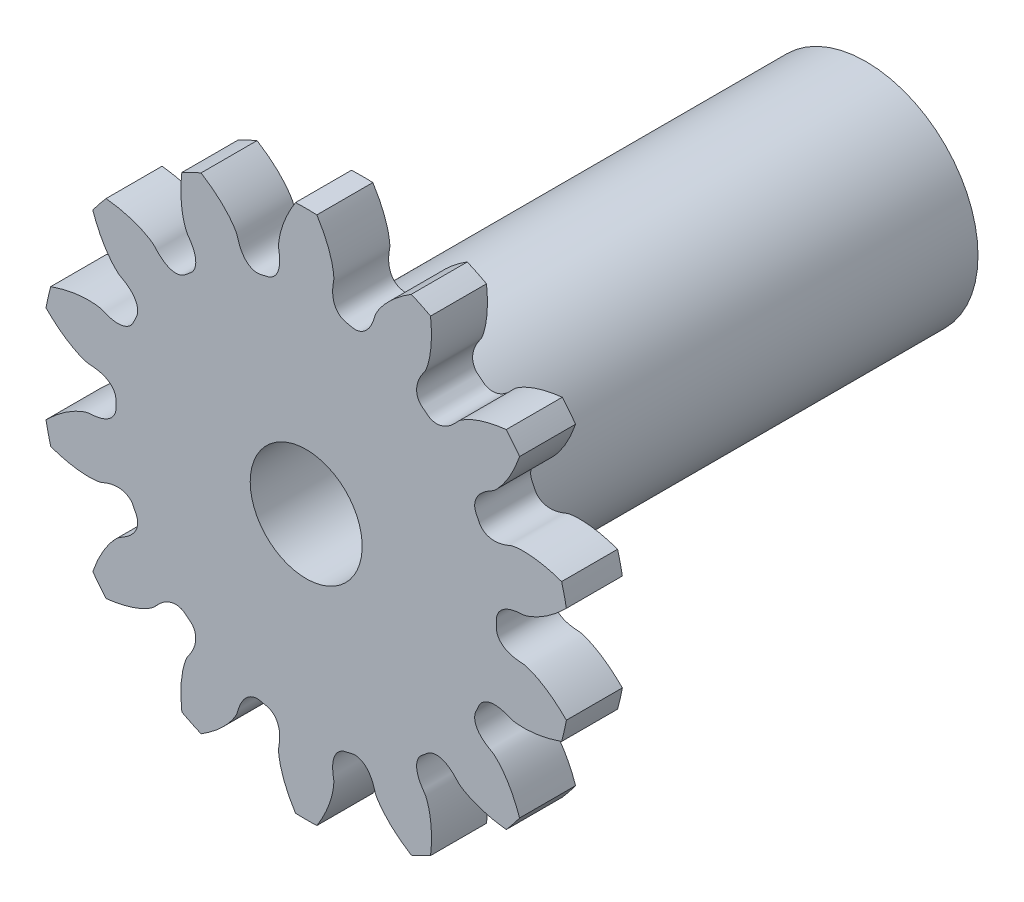
SolidWorks part; units mm, degrees
ref_plane "Alzado" through (0, 0, 0) normal (0, 0, 1) x (1, 0, 0)
ref_plane "Planta" through (0, 0, 0) normal (0, 1, 0) x (1, 0, 0)
ref_plane "Vista lateral" through (0, 0, 0) normal (1, 0, 0) x (0, 0, -1)
ref_axis "Eje1" through (0, 0, 55) along (0, 0, -1)
sketch "SketchRevolveSpur02" plane through (0, 0, 0) normal (1, 0, 0) x (0, 0, -1)
  line L0 (0, 0) -> (1, 0) construction
  line L1 (-0.5, 0) -> (-0.5, 1.1818)
  line L2 (-0.5, 1.1818) -> (-0.25, 1.1818)
  line L3 (-0.25, 1.1818) -> (-0.25, 0)
  line L4 (-0.25, 0) -> (-0.5, 0)
  dimension "D1" = 0.25
revolve "Spur02" add sketch "SketchRevolveSpur02" angle 360 about L0
sketch "SketchToothSpur02" plane through (0, 0, 0) normal (0, 0, 1) x (1, 0, 0)
  arc A0 (1.1682, 0.2227) -> (1.1682, -0.2227) centre (0, 0) cw
  spline S0 degree 3 poles (1.1682, -0.2227) (1.1575, -0.2117) (1.1414, -0.1961) (1.1195, -0.1771) (1.104, -0.1645) (1.089, -0.1533) (1.0747, -0.1432) (1.061, -0.1344) (1.048, -0.1266) (1.0358, -0.1199) (1.0245, -0.1142) (1.014, -0.1093) (1.0046, -0.1054) (0.9961, -0.1021) (0.9887, -0.0996) (0.9823, -0.0977) (0.9738, -0.0954) (0.9644, -0.0944) (0.9543, -0.0941) (0.9465, -0.0934) (0.9389, -0.0924) (0.9315, -0.0913) (0.9244, -0.0898) (0.9175, -0.0881) (0.9108, -0.0861) (0.9043, -0.0838) (0.8981, -0.0813) (0.892, -0.0784) (0.8862, -0.0751) (0.8806, -0.0714) (0.8752, -0.0673) (0.87, -0.0627) (0.8651, -0.0575) (0.8606, -0.0516) (0.8566, -0.0449) (0.8533, -0.0376) (0.8508, -0.0295) (0.8496, -0.0218) (0.8491, -0.0119) (0.8497, 0) (0.8491, 0.0119) (0.8496, 0.0218) (0.8508, 0.0295) (0.8533, 0.0376) (0.8566, 0.0449) (0.8606, 0.0516) (0.8651, 0.0575) (0.87, 0.0627) (0.8752, 0.0673) (0.8806, 0.0714) (0.8862, 0.0751) (0.892, 0.0784) (0.8981, 0.0813) (0.9043, 0.0838) (0.9108, 0.0861) (0.9175, 0.0881) (0.9244, 0.0898) (0.9315, 0.0913) (0.9389, 0.0924) (0.9465, 0.0934) (0.9543, 0.0941) (0.9644, 0.0944) (0.9738, 0.0954) (0.9823, 0.0977) (0.9887, 0.0996) (0.9961, 0.1021) (1.0046, 0.1054) (1.014, 0.1093) (1.0245, 0.1142) (1.0358, 0.1199) (1.048, 0.1266) (1.061, 0.1344) (1.0747, 0.1432) (1.089, 0.1533) (1.104, 0.1645) (1.1195, 0.1771) (1.1414, 0.1961) (1.1575, 0.2117) (1.1682, 0.2227) knots 0 0 0 0 0.0554 0.080914 0.104969 0.127567 0.148706 0.168388 0.186612 0.203378 0.218686 0.232536 0.244928 0.255863 0.265339 0.273357 0.279918 0.297272 0.307044 0.316542 0.325781 0.334777 0.343546 0.352112 0.360499 0.368737 0.376863 0.384917 0.39295 0.401018 0.409187 0.41753 0.426123 0.43504 0.444343 0.454063 0.464189 0.474651 0.482386 0.5 0.517614 0.525349 0.535811 0.545937 0.555657 0.56496 0.573877 0.58247 0.590813 0.598982 0.60705 0.615083 0.623137 0.631263 0.639501 0.647888 0.656454 0.665223 0.674219 0.683458 0.692956 0.702728 0.720082 0.726643 0.734661 0.744137 0.755072 0.767464 0.781314 0.796622 0.813388 0.831612 0.851294 0.872433 0.895031 0.919086 0.9446 1 1 1 1
extrude "ToothExtrudeCutSpur02" cut sketch "SketchToothSpur02" against normal blind 0.5 and the other way blind 0.5
pattern_circular "PatternSpur02" count 14 every 25.714 about axis through (0, 0, 55) along (0, 0, -1) of "ToothExtrudeCutSpur02"
sketch "AuxiliarySketchSpur02" plane through (0, 0, 0) normal (0, 0, 1) x (1, 0, 0)
  circle A0 centre (0, 0) radius 1.0341 construction
  circle A1 centre (0, 0) radius 0.9717 construction
  circle A2 centre (0, 0) radius 0.977 construction
  circle A3 centre (0, 0) radius 1.1818 construction
  circle A4 centre (0, 0) radius 0.8494 construction
  dimension "PitchDiameter" = 2.0682
  dimension "BaseDiameter" = 1.9435
  dimension "FormDiameter" = 1.9539
  dimension "MajorDiameter" = 2.3636
  dimension "MinorDiameter" = 1.6989
sketch "Croquis5" plane through (0, 0, 0.25) normal (0, 0, -1) x (-1, 0, 0)
  circle A0 centre (0, 0) radius 0.5
  circle A1 centre (0, 0) radius 0.25
  dimension "D1" = 1
  dimension "D2" = 0.5
extrude "Saliente-Extruir5" add sketch "Croquis5" along normal blind 2.25
sketch "Croquis6" plane through (0, 0, 0.25) normal (0, 0, -1) x (-1, 0, 0)
  circle A0 centre (0, 0) radius 0.25 construction
  circle A1 centre (0, 0) radius 0.25
extrude "Cortar-Extruir1" cut sketch "Croquis6" against normal through all
